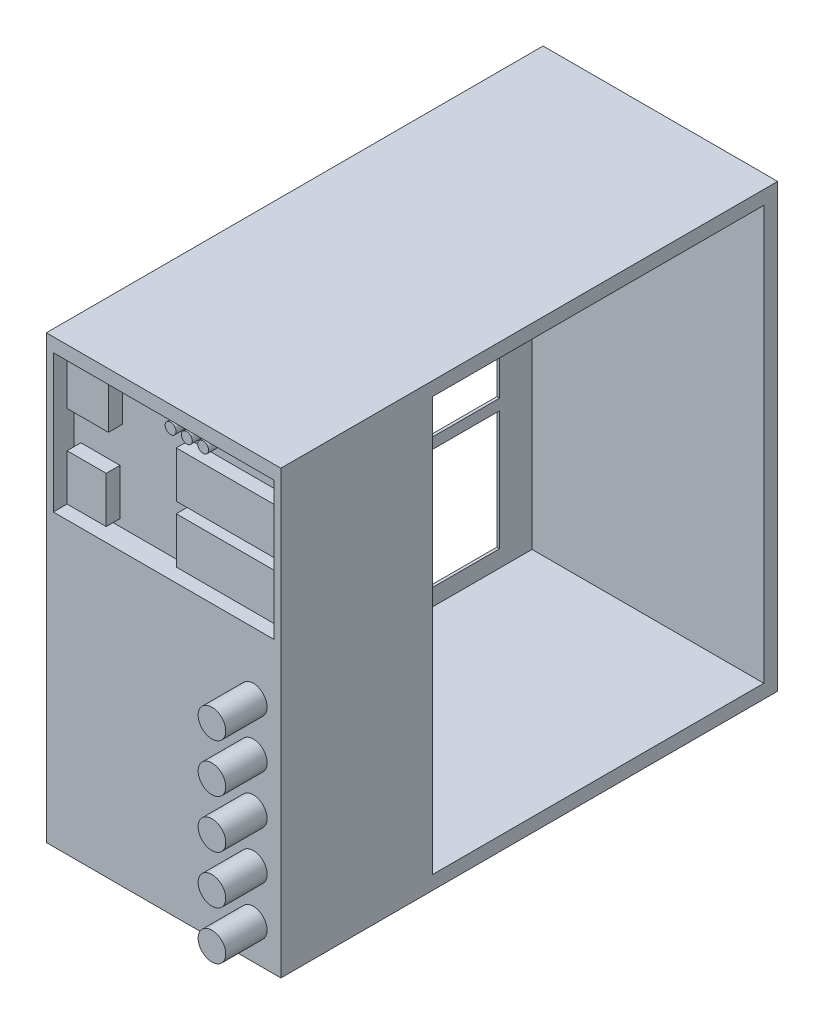
SolidWorks part; units mm, degrees
ref_plane "Front Plane" through (0, 0, 0) normal (0, 0, 1) x (1, 0, 0)
ref_plane "Top Plane" through (0, 0, 0) normal (0, 1, 0) x (1, 0, 0)
ref_plane "Right Plane" through (0, 0, 0) normal (1, 0, 0) x (0, 0, -1)
sketch "Sketch2" plane through (0, 0, 0) normal (0, 0, 1) x (1, 0, 0)
  line L1 (-215.9, -406.4) -> (215.9, -406.4)
  line L2 (-215.9, -406.4) -> (-215.9, 406.4)
  line L3 (-215.9, 406.4) -> (215.9, 406.4)
  line L4 (215.9, -406.4) -> (215.9, 406.4)
  line L5 (-215.9, -406.4) -> (215.9, 406.4) construction
  line L6 (-215.9, 406.4) -> (215.9, -406.4) construction
  point P0 (0, 0)
  dimension "D1" = 431.8
  dimension "D2" = 812.8
extrude "Boss-Extrude1" add sketch "Sketch2" along normal mid plane 914.4
sketch "Sketch3" plane through (0, 0, 457.2) normal (0, 0, 1) x (1, 0, 0)
  line L0 (0, 0) -> (0, 406.4) construction
  line L1 (-215.9, 406.4) -> (215.9, 406.4) construction
  line L3 (-203.2, 127) -> (203.2, 127)
  line L4 (-203.2, 127) -> (-203.2, 381)
  line L5 (-203.2, 381) -> (203.2, 381)
  line L6 (203.2, 127) -> (203.2, 381)
  line L7 (-203.2, 127) -> (203.2, 381) construction
  line L8 (-203.2, 381) -> (203.2, 127) construction
  line L9 (215.9, -406.4) -> (215.9, 406.4) construction
  line L13 (-215.9, -406.4) -> (215.9, -406.4) construction
  line L14 (215.9, -406.4) -> (215.9, 406.4) construction
  circle A0 centre (165.1, -342.9) radius 25.4
  circle A1 centre (165.1, -254) radius 25.4
  circle A2 centre (165.1, -165.1) radius 25.4
  circle A3 centre (165.1, -76.2) radius 25.4
  circle A4 centre (165.1, 12.7) radius 25.4
  point P5 (0, 254)
  dimension "D4" = 50.8
  dimension "D5" = 5
  dimension "D1" = 25.4
  dimension "D2" = 12.7
  dimension "D3" = 254
  dimension "D6" = 63.5
  dimension "D7" = 50.8
  dimension "D8" = 88.9
extrude "Cut-Extrude1" cut sketch "Sketch3" against normal blind 38.1 contours L4 L5 L6 L3
extrude "Boss-Extrude2" add sketch "Sketch3<4>" along normal blind 76.2 contours A0 | A1 | A2 | A3 | A4
sketch "Sketch3<4>" plane through (0, 0, 457.2) normal (0, 0, 1) x (1, 0, 0) same geometry as "Sketch3"
sketch "Sketch5" plane through (0, 0, 419.1) normal (0, 0, 1) x (1, 0, 0)
  line L0 (-203.2, 381) -> (203.2, 381) construction
  line L1 (-190.5, 292.1) -> (-114.3, 292.1)
  line L2 (-190.5, 292.1) -> (-190.5, 368.3)
  line L3 (-190.5, 368.3) -> (-114.3, 368.3)
  line L4 (-114.3, 292.1) -> (-114.3, 368.3)
  line L5 (-190.5, 292.1) -> (-114.3, 368.3) construction
  line L6 (-190.5, 368.3) -> (-114.3, 292.1) construction
  line L7 (-203.2, 127) -> (-203.2, 381) construction
  line L8 (203.2, 127) -> (203.2, 381) construction
  line L9 (10.5, 139.7) -> (190.5, 139.7)
  line L10 (10.5, 139.7) -> (10.5, 224.7)
  line L11 (10.5, 329.7) -> (190.5, 329.7)
  line L12 (190.5, 139.7) -> (190.5, 224.7)
  line L13 (10.5, 139.7) -> (190.5, 329.7) construction
  line L14 (10.5, 329.7) -> (190.5, 139.7) construction
  line L15 (-203.2, 127) -> (203.2, 127) construction
  line L16 (-203.2, 127) -> (203.2, 127) construction
  line L17 (-118.5, 139.7) -> (-190.5, 139.7)
  line L18 (-118.5, 139.7) -> (-118.5, 224.7)
  line L19 (-118.5, 224.7) -> (-190.5, 224.7)
  line L20 (-190.5, 139.7) -> (-190.5, 224.7)
  line L21 (-118.5, 139.7) -> (-190.5, 224.7) construction
  line L22 (-118.5, 224.7) -> (-190.5, 139.7) construction
  line L23 (-203.2, 381) -> (203.2, 381) construction
  line L24 (0, 0) -> (0, 355.6) construction
  line L25 (-27.6, 234.7) -> (152.4, 234.7) construction
  line L26 (10.5, 244.7) -> (190.5, 244.7)
  line L27 (10.5, 224.7) -> (190.5, 224.7)
  line L28 (10.5, 244.7) -> (10.5, 329.7)
  line L29 (190.5, 244.7) -> (190.5, 329.7)
  circle A0 centre (0, 355.6) radius 10
  circle A1 centre (30, 355.6) radius 10
  circle A2 centre (60, 355.6) radius 10
  point P0 (-152.4, 330.2)
  point P5 (100.5, 234.7)
  point P18 (-154.5, 182.2)
  dimension "D13" = 20
  dimension "D17" = 10
  dimension "D1" = 76.2
  dimension "D2" = 76.2
  dimension "D3" = 12.7
  dimension "D4" = 12.7
  dimension "D5" = 12.7
  dimension "D6" = 12.7
  dimension "D7" = 180
  dimension "D9" = 72
  dimension "D10" = 12.7
  dimension "D11" = 12.7
  dimension "D12" = 85
  dimension "D14" = 3
  dimension "D15" = 30
  dimension "D16" = 25.4
  dimension "D18" = 10
  dimension "D19" = 85
  dimension "D20" = 85
extrude "Boss-Extrude3" add sketch "Sketch5" along normal blind 25.4
sketch "Sketch6" plane through (215.9, 0, 0) normal (1, 0, 0) x (0, 0, -1)
  line L1 (-177.8, -381) -> (431.8, -381)
  line L2 (-177.8, -381) -> (-177.8, 381)
  line L3 (-177.8, 381) -> (431.8, 381)
  line L4 (431.8, -381) -> (431.8, 381)
  line L5 (-177.8, -381) -> (431.8, 381) construction
  line L6 (-177.8, 381) -> (431.8, -381) construction
  line L7 (-457.2, 406.4) -> (457.2, 406.4) construction
  line L8 (-457.2, -406.4) -> (457.2, -406.4) construction
  line L9 (457.2, -406.4) -> (457.2, 406.4) construction
  point P0 (127, 0)
  point P9 (121.585, 0)
  dimension "D1" = 609.6
  dimension "D2" = 25.4
  dimension "D3" = 25.4
  dimension "D4" = 25.4
extrude "Cut-Extrude2" cut sketch "Sketch6" against normal through all
sketch "Sketch7" plane through (0, 0, -431.8) normal (0, 0, 1) x (1, 0, 0)
  line L1 (215.9, 381) -> (210.82, 381)
  line L2 (215.9, 381) -> (215.9, -381)
  line L3 (215.9, -381) -> (210.82, -381)
  line L4 (210.82, 381) -> (210.82, -381)
  point P5 (177.8, -355.6)
  point P7 (0, 0)
  point P8 (177.8, 355.6)
  point P10 (0, 0)
  point P11 (0, 0)
  dimension "D1" = 5.08
extrude "Boss-Extrude4" add sketch "Sketch7" along normal up to surface (609.6 mm away) up to face at (0, 0, 177.8)
sketch "Sketch8" plane through (215.9, 0, 0) normal (1, 0, 0) x (0, 0, -1)
  line L0 (-177.8, -381) -> (431.8, -381) construction
  line L2 (-177.8, 381) -> (431.8, 381) construction
  line L3 (-177.8, -381) -> (-177.8, 381) construction
  line L4 (-177.8, -381) -> (431.8, -381)
  line L6 (-177.8, 381) -> (431.8, 381)
  line L7 (-177.8, -381) -> (-177.8, 381)
  line L8 (431.8, 381) -> (431.8, -381)
  dimension "D1" = 609.6
extrude "Cut-Extrude3" cut sketch "Sketch8" against normal through all
sketch "Sketch9" plane through (0, 0, -431.8) normal (0, 0, 1) x (1, 0, 0)
  line L0 (-215.9, -381) -> (215.9, -381) construction
  line L1 (-215.9, 381) -> (-210.82, 381)
  line L2 (-215.9, 381) -> (-215.9, -381)
  line L3 (-215.9, -381) -> (-210.82, -381)
  line L4 (-210.82, 381) -> (-210.82, -381)
  dimension "D1" = 5.08
extrude "Boss-Extrude5" add sketch "Sketch9" along normal up to surface (609.6 mm away) up to face at (0, 0, 177.8)
sketch "Sketch10" plane through (-215.9, 0, 0) normal (-1, 0, 0) x (0, 0, 1)
  line L0 (177.8, 381) -> (-431.8, 381) construction
  line L1 (177.8, -381) -> (177.8, 381) construction
  line L2 (177.8, -381) -> (-431.8, -381) construction
  line L3 (-431.8, -381) -> (-431.8, 381) construction
  line L4 (177.8, 381) -> (-431.8, 381)
  line L5 (177.8, -381) -> (177.8, 381)
  line L6 (177.8, -381) -> (-431.8, -381)
  line L7 (-431.8, -381) -> (-431.8, 381)
  line L8 (-127, 381) -> (-127, 43.6792) construction
  line L9 (-372, 350) -> (-152, 350)
  line L10 (-372, 350) -> (-372, 130)
  line L11 (-372, 130) -> (-152, 130)
  line L12 (-152, 350) -> (-152, 130)
  line L13 (-102, 350) -> (118, 350)
  line L14 (-102, 350) -> (-102, 130)
  line L15 (-102, 130) -> (118, 130)
  line L16 (118, 350) -> (118, 130)
  line L17 (-152, 130) -> (-127, 130) construction
  line L18 (-102, 130) -> (-127, 130) construction
  line L19 (-372, -110) -> (-152, -110)
  line L20 (-372, 110) -> (-372, -110)
  line L21 (-372, 110) -> (-152, 110)
  line L22 (-152, 110) -> (-152, -110)
  line L23 (-102, 110) -> (-102, -110)
  line L24 (-102, 110) -> (118, 110)
  line L25 (118, 110) -> (118, -110)
  line L26 (-102, -110) -> (118, -110)
  line L27 (-372, -350) -> (-152, -350)
  line L28 (-372, -130) -> (-372, -350)
  line L29 (-372, -130) -> (-152, -130)
  line L30 (-152, -130) -> (-152, -350)
  line L31 (-102, -130) -> (-102, -350)
  line L32 (-102, -130) -> (118, -130)
  line L33 (118, -130) -> (118, -350)
  line L34 (-102, -350) -> (118, -350)
  line L35 (-431.8, 0) -> (177.8, 0) construction
  dimension "D1" = 220
  dimension "D2" = 20
  dimension "D3" = 50
  dimension "D4" = 220
  dimension "D5" = 3
  dimension "D6" = 110
  dimension "D7" = 25
extrude "Cut-Extrude5" cut sketch "Sketch10" against normal blind 25.4 contours L12 L9 L10 L11 | L22 L21 L20 L19 | L30 L29 L28 L27 | L31 L34 L33 L32 | L16 L13 L14 L15 | L23 L26 L25 L24 region at (-215.9, 240, -262) region at (-215.9, 240, 8) region at (-215.9, 0, -262) region at (-215.9, 0, 8) region at (-215.9, -240, -262) region at (-215.9, -240, 8)
